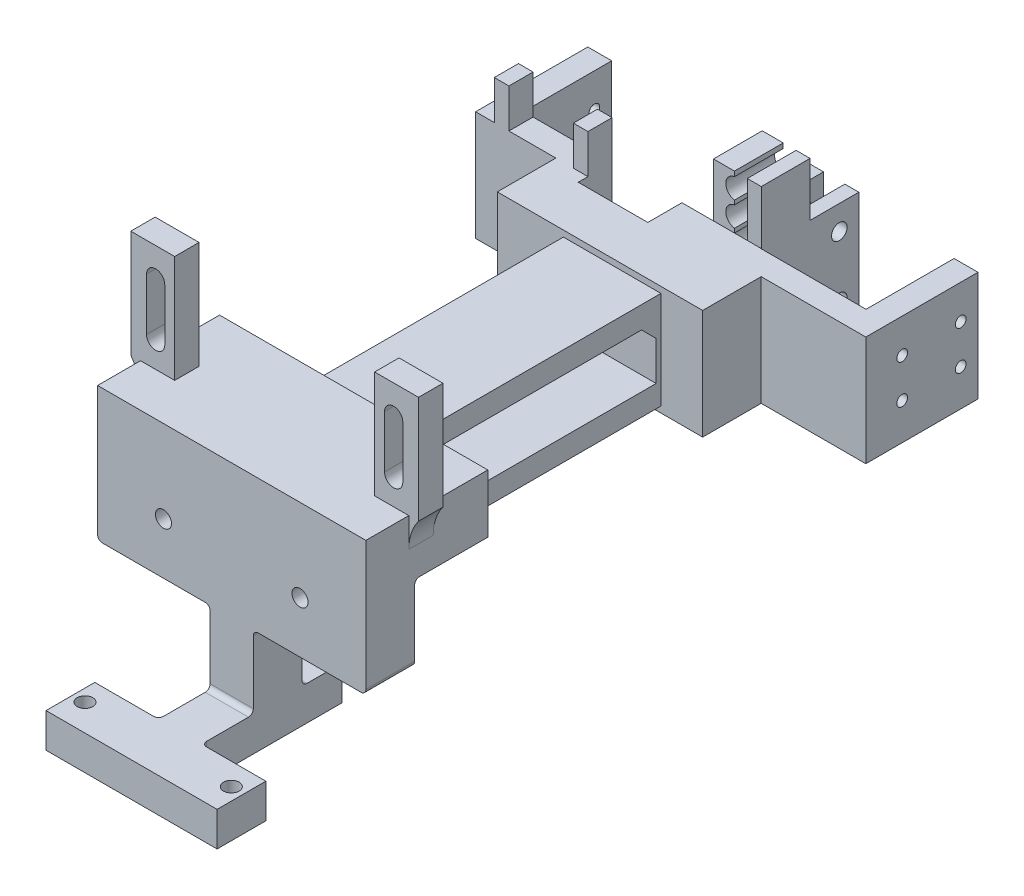
SolidWorks part; units mm, degrees
ref_plane "Front Plane" through (0, 0, 0) normal (0, 0, 1) x (1, 0, 0)
ref_plane "Top Plane" through (0, 0, 0) normal (0, 1, 0) x (1, 0, 0)
ref_plane "Right Plane" through (0, 0, 0) normal (1, 0, 0) x (0, 0, -1)
sketch "草图1" plane through (0, 0, 0) normal (0, 0, 1) x (1, 0, 0)
  line L0 (0, 0) -> (8.5606, 9.7835) construction
  line L1 (-17.5, 20) -> (17.5, 20)
  line L2 (-17.5, 20) -> (-17.5, -20)
  line L3 (-17.5, -20) -> (17.5, -20)
  line L4 (17.5, 20) -> (17.5, -20)
  line L5 (-17.5, 20) -> (0, 0) construction
  line L6 (-17.5, -20) -> (-8.5606, -9.7835) construction
  line L7 (8.5606, -9.7835) -> (17.5, -20) construction
  arc A0 (-12.9135, -1.4975) -> (-8.5606, -9.7835) centre (0, 0) ccw construction
  arc A5 (-1.4975, 12.9135) -> (-12.9135, 1.4975) centre (0, 0) ccw construction
  arc A6 (1.4975, -12.9135) -> (12.9135, -1.4975) centre (0, 0) ccw construction
  arc A8 (12.9135, 1.4975) -> (1.4975, 12.9135) centre (0, 0) ccw construction
  point P0 (0, 0)
  point P19 (0, 0)
  dimension "D1" = 26
  dimension "D2" = 35
  dimension "D3" = 40
extrude "凸台-拉伸1" add sketch "草图1" along normal blind 5
sketch "草图2" plane through (0, 0, 5) normal (0, 0, 1) x (1, 0, 0)
  line L1 (-10, 10) -> (10, 10)
  line L2 (-10, 10) -> (-10, -10)
  line L3 (-10, -10) -> (10, -10)
  line L4 (10, 10) -> (10, -10)
  line L5 (-10, 10) -> (10, -10) construction
  line L6 (-10, -10) -> (10, 10) construction
  point P0 (0, 0)
  dimension "D1" = 20
  dimension "D2" = 20
extrude "凸台-拉伸2" add sketch "草图2" along normal blind 65
sketch "草图3" plane through (-10, 0, 0) normal (-1, 0, 0) x (0, 0, 1)
  line L1 (9.5, -5.5) -> (65.5, -5.5)
  line L2 (65.5, -5.5) -> (65.5, 5.5)
  line L3 (65.5, 5.5) -> (9.5, 5.5)
  line L4 (5, 10) -> (5, -10)
  line L5 (5, -10) -> (70, -10)
  line L6 (70, -10) -> (70, 10)
  line L7 (70, 10) -> (5, 10)
  line L8 (5, 10) -> (5, -10)
  line L9 (5, -10) -> (70, -10)
  line L10 (70, -10) -> (70, 10)
  line L11 (70, 10) -> (5, 10)
  line L12 (9.5, 5.5) -> (5, 5.5)
  line L13 (5, 5.5) -> (5, -5.5)
  line L14 (5, -5.5) -> (9.5, -5.5)
  line L16 (9.5, 5.5) -> (9.5, -5.5) construction
  dimension "D1" = 0
  dimension "D2" = 4.5
extrude "切除-拉伸1" cut sketch "草图3" against normal through all contours L3 L16 L1 L2 | L16 L12 L8 L14
sketch "草图5" plane through (0, 0, 70) normal (0, 0, 1) x (1, 0, 0)
  line L1 (-27.5, 10) -> (27.5, 10)
  line L2 (-27.5, 10) -> (-27.5, -10)
  line L3 (-27.5, -10) -> (27.5, -10)
  line L4 (27.5, 10) -> (27.5, -10)
  line L5 (-27.5, 10) -> (27.5, -10) construction
  line L6 (-27.5, -10) -> (27.5, 10) construction
  point P0 (0, 0)
  dimension "D1" = 20
  dimension "D2" = 55
extrude "凸台-拉伸3" add sketch "草图5" along normal blind 25
sketch "草图6" plane through (0, 0, 95) normal (0, 0, 1) x (1, 0, 0)
  circle A0 centre (-10.5, 24.851) radius 28
  dimension "D1" = 56
sketch "草图7" plane through (0, 0, 95) normal (0, 0, 1) x (1, 0, 0)
  line L0 (-27.5, 0) -> (27.5, 0) construction
  circle A0 centre (-14, 0) radius 1.6
  circle A1 centre (14, 0) radius 1.6
  dimension "D1" = 3.2
  dimension "D2" = 3.2
  dimension "D3" = 14
sketch "草图8" plane through (0, 0, 95) normal (0, 0, 1) x (1, 0, 0)
  line L0 (0, 0) -> (0, 38.7241) construction
  line L1 (17.5, 20) -> (-17.5, 20) construction
  circle A0 centre (0, 20) radius 1.9754 construction
  circle A1 centre (0, 20) radius 14.0625
  dimension "D1" = 28.125
sketch "草图9" plane through (0, 0, 95) normal (0, 0, 1) x (1, 0, 0)
  line L1 (0, -51.5757) -> (0, 13.3029) construction
  line L2 (14, -3.0427) -> (-14, -3.0427) construction
  line L3 (27.5, 10) -> (-27.5, 10) construction
  line L4 (-8.5, -51.5757) -> (8.5, -51.5757) construction
  circle A1 centre (-14, -3.0427) radius 1.65
  circle A2 centre (14, -3.0427) radius 1.65
  dimension "D1" = 14
  dimension "D3" = 3.3
  dimension "D2" = 13.0427
  dimension "D4" = 14
extrude "切除-拉伸3" cut sketch "草图9" against normal blind 27
sketch "草图10" plane through (0, 10, 0) normal (0, 1, 0) x (1, 0, 0)
  line L1 (-27.5, -70) -> (27.5, -70)
  line L2 (-27.5, -70) -> (-27.5, -95)
  line L3 (-27.5, -95) -> (27.5, -95)
  line L4 (27.5, -70) -> (27.5, -95)
extrude "凸台-拉伸4" add sketch "草图10" along normal blind 4.9
sketch "草图11" plane through (0, 14.9, 0) normal (0, 1, 0) x (1, 0, 0)
  line L0 (-27.5, -70) -> (-27.5, -95) construction
  line L1 (-27.5, -81.2) -> (-20.5, -81.2)
  line L2 (-27.5, -81.2) -> (-27.5, -86.2)
  line L3 (-27.5, -86.2) -> (-20.5, -86.2)
  line L4 (-20.5, -81.2) -> (-20.5, -86.2)
  line L5 (-20.5, -94.35) -> (-20.5, -85.7) construction
  line L6 (-25.1, -86.2) -> (-20.5, -86.2) construction
  line L7 (27.5, -95) -> (27.5, -70) construction
  line L8 (27.5, -86.2) -> (20.5, -86.2)
  line L9 (27.5, -86.2) -> (27.5, -81.2)
  line L10 (27.5, -81.2) -> (20.5, -81.2)
  line L11 (20.5, -86.2) -> (20.5, -81.2)
  line L12 (20.5, -65.7) -> (20.5, -85.7) construction
  dimension "D1" = 5
  dimension "D2" = 5
extrude "凸台-拉伸5" add sketch "草图11" along normal blind 21
sketch "草图12" plane through (0, 0, 86.2) normal (0, 0, 1) x (1, 0, 0)
  circle A0 centre (-24.4, 29.9) radius 1.5
  circle A1 centre (-24.4, 19.9) radius 1.5
  circle A2 centre (24.4, 19.9) radius 1.5
  circle A3 centre (24.4, 29.9) radius 1.5
  dimension "D1" = 3
extrude "切除-拉伸4" [suppressed] cut sketch "草图12" against normal blind 21
chamfer "倒角2" distance 10 angle 45 1 edges at (0, -5.5, 65.5)
chamfer "倒角3" distance 3 angle 45 1 edges at (0, 10, 70)
chamfer "倒角4" distance 2 angle 45 1 edges at (0, -10, 5)
sketch "草图13" plane through (0, 0, 5) normal (0, 0, 1) x (1, 0, 0)
  circle A0 centre (0, -13) radius 2.5
  dimension "D1" = 5
sketch "草图14" plane through (27.5, 0, 0) normal (1, 0, 0) x (0, 0, -1)
  circle A0 centre (-79.3333, -5.771) radius 1.5
  circle A1 centre (-65.7124, -5.771) radius 1.5
extrude "切除-拉伸6" [suppressed] cut sketch "草图14" against normal through all
sketch "草图15" plane through (0, 0, 70) normal (0, 0, -1) x (-1, 0, 0)
  line L0 (0, 0) -> (0, -6.8076) construction
  line L1 (10, 13) -> (10, -10) construction
  line L2 (10, 1.9573) -> (29.1308, 1.9573)
  line L3 (10, 1.9573) -> (10, -8.0427)
  line L5 (29.1308, 1.9573) -> (29.1308, -8.0427)
  line L6 (14, -3.0427) -> (8.2324, -3.0427) construction
  line L7 (-14, -3.0427) -> (-8.2324, -3.0427) construction
  line L8 (-29.1308, 1.9573) -> (-29.1308, -8.0427)
  line L10 (-10, 1.9573) -> (-10, -8.0427)
  line L11 (-10, 1.9573) -> (-29.1308, 1.9573)
  line L14 (-29.1308, -8.0427) -> (-29.1308, -10)
  line L15 (-29.1308, -10) -> (-10, -10)
  line L16 (-10, -8.0427) -> (-10, -10)
  line L18 (10, -8.0427) -> (10, -10)
  line L19 (10, -10) -> (29.1308, -10)
  line L20 (29.1308, -8.0427) -> (29.1308, -10)
  point P13 (10, -3.0427)
  dimension "D1" = 10
extrude "切除-拉伸7" cut sketch "草图15" against normal blind 15
sketch "草图16" plane through (-10, 0, 0) normal (-1, 0, 0) x (0, 0, 1)
  line L0 (5, -5.5) -> (55.5, -5.5) construction
  line L1 (5, 5.5) -> (17.9846, 5.5)
  line L2 (5, 5.5) -> (5, -5.5)
  line L3 (5, -5.5) -> (17.9846, -5.5)
  line L4 (17.9846, 5.5) -> (17.9846, -5.5)
extrude "凸台-拉伸6" add sketch "草图16" against normal up to surface (20 mm away) up to face at (10, 0.7242, 45.4231)
chamfer "倒角5" distance 3 angle 45 1 edges at (0, 5.5, 17.9846)
sketch "草图19" plane through (0, 0, 86.2) normal (0, 0, 1) x (1, 0, 0)
  circle A0 centre (-24.4, 29.9) radius 1.6
  circle A1 centre (-24.4, 19.9) radius 1.6
  circle A2 centre (24.4, 19.9) radius 1.6
  circle A3 centre (24.4, 29.9) radius 1.6
  dimension "D1" = 3.2
extrude "切除-拉伸10" cut sketch "草图19" against normal blind 10
fillet "圆角1" radius 5 4 edges at (17.5, 20, 2.5) (17.5, -20, 2.5) (-17.5, -20, 2.5) (-17.5, 20, 2.5)
ref_plane "基准面1" through (0, 0, 0) normal (0, 1, 0) x (1, 0, 0)
sketch "草图20" plane through (-17.5, 0, 0) normal (-1, 0, 0) x (0, 0, 1)
  line L0 (0, 15) -> (0, -15) construction
  line L1 (0, 11.25) -> (5, 11.25)
  line L2 (0, 11.25) -> (0, -11.25)
  line L3 (0, -11.25) -> (5, -11.25)
  line L4 (5, 11.25) -> (5, -11.25)
  line L5 (0, 11.25) -> (-6.5, 11.25) construction
  line L6 (5, 15) -> (5, -15) construction
extrude "凸台-拉伸7" add sketch "草图20" along normal up to surface (17.5 mm away)
sketch "草图21" plane through (-35, 0, 0) normal (-1, 0, 0) x (0, 0, 1)
  line L4 (0, -11.25) -> (5, -11.25)
  line L5 (5, -11.25) -> (5, 11.25)
  line L6 (5, 11.25) -> (0, 11.25)
  line L7 (0, 11.25) -> (0, -11.25)
  line L8 (0, -11.25) -> (5, -11.25)
  line L9 (5, -11.25) -> (5, 11.25)
  line L10 (5, 11.25) -> (0, 11.25)
  line L11 (0, 11.25) -> (0, -11.25)
  dimension "D1" = 0
extrude "凸台-拉伸8" add sketch "草图21" along normal blind 5
sketch "草图22" plane through (0, 0, 0) normal (0, 0, -1) x (-1, 0, 0)
  line L0 (40, 11.25) -> (17.5, 11.25) construction
  line L1 (40, -11.25) -> (35, -11.25)
  line L2 (40, -11.25) -> (40, 11.25)
  line L3 (40, 11.25) -> (35, 11.25)
  line L4 (35, -11.25) -> (35, 11.25)
  line L5 (35, -11.25) -> (35, 11.25) construction
extrude "凸台-拉伸9" add sketch "草图22" along normal blind 10
sketch "草图23" plane through (0, 0, 0) normal (0, 0, -1) x (-1, 0, 0)
  line L0 (35, -11.25) -> (17.5, -11.25) construction
  line L1 (18, -11.25) -> (13, -11.25)
  line L2 (18, -11.25) -> (18, 11.25)
  line L3 (18, 11.25) -> (13, 11.25)
  line L4 (13, -11.25) -> (13, 11.25)
  line L5 (18, -11.25) -> (18, 11.25) construction
  dimension "D1" = 5
extrude "凸台-拉伸10" add sketch "草图23" along normal blind 10
sketch "草图24" plane through (-18, 0, 0) normal (-1, 0, 0) x (0, 0, 1)
  line L1 (-10, 11.25) -> (-6.7, 11.25)
  line L2 (-10, 11.25) -> (-10, -11.25)
  line L3 (-10, -11.25) -> (-6.7, -11.25)
  line L4 (-6.7, 11.25) -> (-6.7, -11.25)
  dimension "D1" = 3.3
extrude "凸台-拉伸11" add sketch "草图24" along normal blind 4
sketch "草图25" plane through (-35, 0, 0) normal (1, 0, 0) x (0, 0, -1)
  line L0 (10, -11.25) -> (0, -11.25) construction
  line L1 (10, 11.25) -> (6.7, 11.25)
  line L2 (10, 11.25) -> (10, -11.25)
  line L3 (10, -11.25) -> (6.7, -11.25)
  line L4 (6.7, 11.25) -> (6.7, -11.25)
  dimension "D1" = 3.3
sketch "草图26" plane through (17.5, 0, 0) normal (1, 0, 0) x (0, 0, -1)
  line L1 (-5, 11.25) -> (0, 11.25)
  line L2 (-5, 11.25) -> (-5, -11.25)
  line L3 (-5, -11.25) -> (0, -11.25)
  line L4 (0, 11.25) -> (0, -11.25)
extrude "凸台-拉伸13" add sketch "草图26" along normal up to surface (17.5 mm away)
sketch "草图27" plane through (35, 0, 0) normal (1, 0, 0) x (0, 0, -1)
  line L4 (-5, -11.25) -> (0, -11.25)
  line L5 (0, -11.25) -> (0, 11.25)
  line L6 (0, 11.25) -> (-5, 11.25)
  line L7 (-5, 11.25) -> (-5, -11.25)
  line L8 (-5, -11.25) -> (0, -11.25)
  line L9 (0, -11.25) -> (0, 11.25)
  line L10 (0, 11.25) -> (-5, 11.25)
  line L11 (-5, 11.25) -> (-5, -11.25)
  dimension "D1" = 0
extrude "凸台-拉伸14" add sketch "草图27" along normal blind 5
sketch "草图28" plane through (0, 0, 0) normal (0, 0, -1) x (-1, 0, 0)
  line L0 (-40, -11.25) -> (-17.5, -11.25) construction
  line L1 (-40, 11.25) -> (-35, 11.25)
  line L2 (-40, 11.25) -> (-40, -11.25)
  line L3 (-40, -11.25) -> (-35, -11.25)
  line L4 (-35, 11.25) -> (-35, -11.25)
  line L5 (-35, -11.25) -> (-35, 11.25) construction
extrude "凸台-拉伸15" add sketch "草图28" along normal up to surface (10 mm away) up to face at (-17.5, 0, -10)
sketch "草图29" plane through (0, 0, 0) normal (0, 0, -1) x (-1, 0, 0)
  line L0 (-35, 11.25) -> (-17.5, 11.25) construction
  line L1 (-18, 11.25) -> (-13, 11.25)
  line L2 (-18, 11.25) -> (-18, -11.25)
  line L3 (-18, -11.25) -> (-13, -11.25)
  line L4 (-13, 11.25) -> (-13, -11.25)
  line L5 (-18, -11.25) -> (-18, 11.25) construction
  line L6 (-35, -11.25) -> (-17.5, -11.25) construction
  dimension "D1" = 5
extrude "凸台-拉伸16" add sketch "草图29" along normal up to surface (10 mm away) up to face at (37.5, 0, -10)
sketch "草图30" plane through (35, 0, 0) normal (-1, 0, 0) x (0, 0, 1)
  line L0 (-10, -11.25) -> (0, -11.25) construction
  line L1 (-10, 11.25) -> (-6.6, 11.25)
  line L2 (-10, 11.25) -> (-10, -11.25)
  line L3 (-10, -11.25) -> (-6.6, -11.25)
  line L4 (-6.6, 11.25) -> (-6.6, -11.25)
  dimension "D1" = 3.4
sketch "草图31" plane through (18, 0, 0) normal (1, 0, 0) x (0, 0, -1)
  line L0 (10, 11.25) -> (0, 11.25) construction
  line L1 (10, -11.25) -> (6.6, -11.25)
  line L2 (10, -11.25) -> (10, 11.25)
  line L3 (10, 11.25) -> (6.6, 11.25)
  line L4 (6.6, -11.25) -> (6.6, 11.25)
  dimension "D1" = 3.4
extrude "凸台-拉伸18" add sketch "草图31" along normal blind 4
sketch "草图32" plane through (0, 0, 5) normal (0, 0, 1) x (1, 0, 0)
  circle A0 centre (-32.5, 3.75) radius 1
  circle A1 centre (-32.5, -4.25) radius 1
  circle A2 centre (-20.5, 3.75) radius 1
  circle A3 centre (-20.5, -4.25) radius 1
  circle A4 centre (20.5, 3.75) radius 1
  circle A5 centre (20.5, -4.25) radius 1
  circle A6 centre (32.5, -4.25) radius 1
  circle A7 centre (32.5, 3.75) radius 1
  dimension "D1" = 2
  dimension "D2" = 2
  dimension "D3" = 2
sketch "草图33" plane through (0, -10, 0) normal (0, -1, 0) x (1, 0, 0)
  line L0 (-27.5, 70) -> (-27.5, 85) construction
  line L1 (-27.5, 62.1642) -> (27.5, 62.1642)
  line L2 (-27.5, 62.1642) -> (-27.5, 106.0669)
  line L3 (-27.5, 106.0669) -> (27.5, 106.0669)
  line L4 (27.5, 62.1642) -> (27.5, 106.0669)
extrude "凸台-拉伸19" [suppressed] add sketch "草图33" along normal up to surface (25.5757 mm away)
sketch "草图34" [suppressed] plane through (0, -10, 0) normal (0, 1, 0) x (1, 0, 0)
  line L0 (0, -106.0669) -> (0, -40) construction
  line L1 (27.5, -106.0669) -> (-27.5, -106.0669) construction
  line L2 (27.5, -40) -> (-27.5, -40) construction
  line L4 (-27.5, -40) -> (-6, -40)
  line L5 (-27.5, -40) -> (-27.5, -77.2915)
  line L6 (-27.5, -77.2915) -> (-6, -77.2915)
  line L7 (-6, -40) -> (-6, -77.2915)
  line L8 (27.5, -40) -> (6, -40)
  line L9 (27.5, -40) -> (27.5, -77.2915)
  line L10 (27.5, -77.2915) -> (6, -77.2915)
  line L11 (6, -40) -> (6, -77.2915)
  line L12 (27.5, -106.0669) -> (-27.5, -106.0669)
  line L13 (27.5, -106.0669) -> (27.5, -65)
  line L14 (27.5, -65) -> (-27.5, -65)
  line L15 (-27.5, -106.0669) -> (-27.5, -65)
  dimension "D1" = 6
  dimension "D2" = 6
extrude "切除-拉伸12" [suppressed] cut sketch "草图34" against normal blind 18
sketch "草图35" [suppressed] plane through (0, -35.5757, 0) normal (0, -1, 0) x (1, 0, 0)
  line L0 (-17.5, 85.6) -> (-17.5, 41.6) construction
  line L1 (-27.5, 62.1642) -> (-4.8154, 62.1642)
  line L2 (-27.5, 62.1642) -> (-27.5, 81.8991)
  line L3 (-17.5, 81.8991) -> (-4.8154, 81.8991)
  line L4 (-4.8154, 62.1642) -> (-4.8154, 81.8991)
  line L5 (27.5, 62.1642) -> (3.7618, 62.1642)
  line L6 (27.5, 62.1642) -> (27.5, 81.8624)
  line L7 (17.5, 81.8991) -> (3.7618, 81.8991)
  line L8 (3.7618, 62.1642) -> (3.7618, 81.8991)
  line L9 (-27.5, 106.0669) -> (-17.5, 106.0669)
  line L10 (-27.5, 106.0669) -> (-27.5, 81.8991)
  line L12 (-17.5, 106.0669) -> (-17.5, 81.8991)
  line L14 (27.5, 106.0669) -> (17.5, 106.0669)
  line L17 (17.5, 106.0669) -> (17.5, 81.8991)
  line L19 (27.5, 81.8624) -> (27.5, 106.0669)
extrude "切除-拉伸13" [suppressed] cut sketch "草图35" against normal blind 11
sketch "草图36" [suppressed] plane through (0, -35.5757, 0) normal (0, -1, 0) x (1, 0, 0)
  line L0 (17.5, 106.0669) -> (17.5, 81.8991) construction
  line L1 (-17.5, 81.8991) -> (17.5, 81.8991)
  line L2 (-17.5, 81.8991) -> (-17.5, 95.6286)
  line L3 (-17.5, 95.6286) -> (17.5, 95.6286)
  line L4 (17.5, 81.8991) -> (17.5, 95.6286)
extrude "切除-拉伸14" [suppressed] cut sketch "草图36" against normal blind 5
sketch "草图37" [suppressed] plane through (0, -35.5757, 0) normal (0, -1, 0) x (1, 0, 0)
  line L0 (3.7618, 81.8991) -> (3.7618, 62.1642) construction
  line L1 (-4.8154, 62.1642) -> (3.7618, 62.1642)
  line L2 (-4.8154, 62.1642) -> (-4.8154, 72.6172)
  line L3 (-4.8154, 72.6172) -> (3.7618, 72.6172)
  line L4 (3.7618, 62.1642) -> (3.7618, 72.6172)
extrude "切除-拉伸15" [suppressed] cut sketch "草图37" against normal up to surface (5 mm away)
fillet "圆角2" [suppressed] radius 1
sketch "草图38" [suppressed] plane through (0, -28, 0) normal (0, 1, 0) x (1, 0, 0)
  circle A0 centre (-15, -80.1116) radius 1.5
  circle A1 centre (15, -80.1116) radius 1.5
extrude "切除-拉伸16" [suppressed] cut sketch "草图38" against normal up to surface (7.5757 mm away)
sketch "草图39" plane through (-17.5, 0, 0) normal (-1, 0, 0) x (0, 0, 1)
  line L1 (0, 11.25) -> (7.1368, 11.25)
  line L2 (0, 11.25) -> (0, 24.7683)
  line L3 (0, 24.7683) -> (7.1368, 24.7683)
  line L4 (7.1368, 11.25) -> (7.1368, 24.7683)
  line L5 (0, -11.25) -> (8.1393, -11.25)
  line L6 (0, -11.25) -> (0, -21.7723)
  line L7 (0, -21.7723) -> (8.1393, -21.7723)
  line L8 (8.1393, -11.25) -> (8.1393, -21.7723)
extrude "切除-拉伸17" cut sketch "草图39" against normal up to surface (35 mm away) up to face at (17.5, 13.125, 2.5)
sketch "草图40" plane through (0, -10, 0) normal (0, -1, 0) x (1, 0, 0)
  line L1 (27.5, 85) -> (-27.5, 85)
  line L2 (27.5, 85) -> (27.5, 95)
  line L3 (27.5, 95) -> (-27.5, 95)
  line L4 (-27.5, 85) -> (-27.5, 95)
extrude "凸台-拉伸20" add sketch "草图40" along normal up to surface (25.5757 mm away)
sketch "草图41" plane through (0, 0, 95) normal (0, 0, 1) x (1, 0, 0)
  line L0 (27.5, -35.5757) -> (-27.5, -35.5757) construction
  line L1 (-4.4244, -35.5757) -> (4.4244, -35.5757)
  line L2 (-4.4244, -35.5757) -> (-4.4244, -28.5296)
  line L3 (-4.4244, -28.5296) -> (4.4244, -28.5296)
  line L4 (4.4244, -35.5757) -> (4.4244, -28.5296)
  line L5 (4.4244, -35.5757) -> (-4.4244, -28.5296) construction
  line L6 (0, -37.5757) -> (0, -41.8305) construction
  line L7 (-8.5, -37.5757) -> (8.5, -37.5757) construction
  point P11 (0, -32.0526)
extrude "凸台-拉伸21" add sketch "草图41" along normal up to surface (20.578 mm away)
sketch "草图42" plane through (-4.4244, 0, 0) normal (-1, 0, 0) x (0, 0, 1)
  line L0 (115.578, -28.5296) -> (95, -28.5296) construction
  line L1 (115.578, -35.5757) -> (76.7852, -35.5757)
  line L2 (115.578, -35.5757) -> (115.578, -28.5296)
  line L3 (115.578, -28.5296) -> (76.7852, -28.5296)
  line L4 (76.7852, -35.5757) -> (76.7852, -28.5296)
extrude "凸台-拉伸22" add sketch "草图42" along normal up to surface (13.0756 mm away) and the other way blind 22
sketch "草图43" plane through (0, -35.5757, 0) normal (0, -1, 0) x (1, 0, 0)
  line L1 (27.5, 76.7852) -> (4.4244, 76.7852)
  line L2 (27.5, 76.7852) -> (27.5, 105.578)
  line L3 (27.5, 105.578) -> (4.4244, 105.578)
  line L4 (4.4244, 76.7852) -> (4.4244, 105.578)
  line L6 (-27.5, 76.7852) -> (-4.4244, 76.7852)
  line L7 (-27.5, 76.7852) -> (-27.5, 105.578)
  line L8 (-27.5, 105.578) -> (-4.4244, 105.578)
  line L9 (-4.4244, 76.7852) -> (-4.4244, 105.578)
  line L11 (17.5756, 76.7852) -> (-17.5, 76.7852) construction
  line L13 (17.5756, 115.578) -> (-17.5, 115.578) construction
  dimension "D1" = 10
extrude "切除-拉伸18" cut sketch "草图43" against normal blind 22
fillet "圆角3" radius 1 11 edges at (-27.5, -13.5757, 90) (27.5, -13.5757, 90) (4.4244, -13.5757, 90) (18.75, 1.9573, 85) (-4.4244, -13.5757, 90) (0, -10, 85) (-18.75, 1.9573, 85) (0, -28.5296, 95) (0, -28.5296, 85) (-4.4244, -32.0526, 105.578) (4.4244, -32.0526, 105.578)
sketch "草图46" plane through (0, 0, 0) normal (0, 0, -1) x (-1, 0, 0)
  line L0 (-13, -11.25) -> (13, -11.25) construction
  line L1 (-13, 11.25) -> (-3.7618, 11.25)
  line L2 (-13, 11.25) -> (-13, -11.25)
  line L3 (-13, -11.25) -> (-3.7618, -11.25)
  line L4 (-3.7618, 11.25) -> (-3.7618, -11.25)
extrude "凸台-拉伸26" add sketch "草图46" along normal blind 10
sketch "草图47" plane through (0, 0, -10) normal (0, 0, -1) x (-1, 0, 0)
  line L0 (0, 120.494) -> (0, -21.6004) construction
  line L1 (-3.7618, 11.25) -> (-22, 11.25) construction
  line L2 (-8.0664, 11.25) -> (-10.7005, 11.25)
  line L3 (-10.7005, 11.25) -> (-10.7005, -11.25)
  line L4 (-22, -11.25) -> (-3.7618, -11.25) construction
  line L5 (-10.7005, -11.25) -> (-6.3328, -11.25)
  line L6 (-6.3328, -11.25) -> (-6.3328, -9.5796) construction
  line L7 (-8.0664, -7.9) -> (-8.0664, -8.75)
  line L8 (-8.0664, -2.9) -> (-8.0664, -3.75)
  line L9 (-8.0664, 7.1) -> (-8.0664, 6.25)
  line L10 (-8.0664, 2.1) -> (-8.0664, 1.25)
  circle A0 centre (0, 109.494) radius 11 construction
  arc A1 (-8.0664, 11.25) -> (-8.0664, 7.1) centre (-8.3894, 9.175) cw
  arc A2 (-8.0664, 6.25) -> (-8.0664, 2.1) centre (-8.3894, 4.175) cw
  arc A3 (-8.0664, 1.25) -> (-8.0664, -2.9) centre (-8.3894, -0.825) cw
  arc A4 (-8.0664, -3.75) -> (-8.0664, -7.9) centre (-8.3894, -5.825) cw
  arc A5 (-8.0664, -8.75) -> (-6.3328, -11.25) centre (-8.3894, -10.825) cw
  dimension "D1" = 2.1
  dimension "D2" = 5
extrude "切除-拉伸19" cut sketch "草图47" against normal blind 10
sketch "草图48" plane through (0, -28.5296, 0) normal (0, 1, 0) x (1, 0, 0)
  circle A0 centre (15, -110.0896) radius 1.6
  circle A1 centre (-15, -110.0896) radius 1.6
  dimension "D1" = 3.2
extrude "切除-拉伸20" cut sketch "草图48" against normal blind 10
sketch "草图49" plane through (0, 0, 86.2) normal (0, 0, 1) x (1, 0, 0)
  line L0 (0, 0) -> (0, 23.1634) construction
  line L1 (-24.4, 29.9) -> (-24.4, 19.1657) construction
  line L2 (-22.5287, 29.9) -> (-22.5287, 19.1657)
  line L3 (-26.2713, 29.9) -> (-26.2713, 19.1657)
  line L4 (24.4, 29.9) -> (24.4, 19.1657) construction
  line L5 (22.5287, 29.9) -> (22.5287, 19.1657)
  line L6 (26.2713, 29.9) -> (26.2713, 19.1657)
  arc A0 (-22.5287, 29.9) -> (-26.2713, 29.9) centre (-24.4, 29.9) ccw
  arc A1 (-26.2713, 19.1657) -> (-22.5287, 19.1657) centre (-24.4, 19.1657) ccw
  arc A2 (22.5287, 29.9) -> (26.2713, 29.9) centre (24.4, 29.9) cw
  arc A3 (26.2713, 19.1657) -> (22.5287, 19.1657) centre (24.4, 19.1657) cw
  point P6 (-24.4, 24.5328)
  point P13 (24.4, 24.5328)
extrude "切除-拉伸21" cut sketch "草图49" against normal blind 10
sketch "草图50" plane through (0, 0, -10) normal (0, 0, -1) x (-1, 0, 0)
  line L0 (-22, -11.25) -> (-10.7005, -11.25) construction
  line L1 (-3.7618, 11.25) -> (-6.3328, 11.25)
  line L2 (-3.7618, 11.25) -> (-3.7618, -11.25)
  line L3 (-3.7618, -11.25) -> (-6.3328, -11.25)
  line L4 (-6.3328, 11.25) -> (-6.3328, -11.25)
  line L5 (-10.7005, 11.25) -> (-13.5656, 11.25)
  line L6 (-10.7005, 11.25) -> (-10.7005, -11.25)
  line L7 (-10.7005, -11.25) -> (-13.5656, -11.25)
  line L8 (-13.5656, 11.25) -> (-13.5656, -11.25)
extrude "凸台-拉伸27" add sketch "草图50" along normal blind 10
sketch "草图53" plane through (0, 11.25, 0) normal (0, 1, 0) x (1, 0, 0)
  line L1 (8.0664, 10) -> (3.7618, 10)
  line L2 (8.0664, 10) -> (8.0664, 0)
  line L3 (8.0664, 0) -> (3.7618, 0)
  line L4 (3.7618, 10) -> (3.7618, 0)
  line L5 (13.5656, 10) -> (10.7005, 10)
  line L6 (13.5656, 10) -> (13.5656, 0)
  line L7 (13.5656, 0) -> (10.7005, 0)
  line L8 (10.7005, 10) -> (10.7005, 0)
extrude "凸台-拉伸28" add sketch "草图53" along normal blind 11
sketch "草图51" plane through (13.5656, 0, 0) normal (1, 0, 0) x (0, 0, -1)
  line L0 (15, 11.25) -> (15, -11.25) construction
  line L1 (20, 11.25) -> (10, 11.25) construction
  line L2 (20, -11.25) -> (10, -11.25) construction
  line L3 (20, 11.25) -> (20, -11.25) construction
  circle A0 centre (16, 6.25) radius 1.6
  circle A1 centre (16, -6.25) radius 1.6
  dimension "D1" = 3.2
  dimension "D2" = 5
  dimension "D3" = 5
  dimension "D4" = 4
extrude "切除-拉伸22" cut sketch "草图51" against normal blind 12
sketch "草图52" plane through (0, 11.25, 0) normal (0, 1, 0) x (1, 0, 0)
  line L0 (-26.5, 0) -> (-26.5, 6.7) construction
  line L1 (-35, 0) -> (-18, 0) construction
  line L2 (0, 0) -> (0, 4.3666) construction
  line L3 (-35.1, 6.75) -> (-17.9, 6.75)
  line L4 (-35.1, 6.75) -> (-35.1, -0.05)
  line L5 (-35.1, -0.05) -> (-17.9, -0.05)
  line L6 (-17.9, 6.75) -> (-17.9, -0.05)
  line L7 (-35.1, 6.75) -> (-17.9, -0.05) construction
  line L8 (-35.1, -0.05) -> (-17.9, 6.75) construction
  line L9 (35.1, -0.05) -> (17.9, -0.05)
  line L10 (17.9, 6.75) -> (17.9, -0.05)
  line L11 (35.1, 6.75) -> (17.9, 6.75)
  line L12 (35.1, 6.75) -> (35.1, -0.05)
  point P4 (-26.5, 3.35)
  dimension "D1" = 17.2
  dimension "D2" = 6.8
extrude "切除-拉伸23" cut sketch "草图52" against normal blind 39
ref_plane "基准面2" through (5.0473, 0, 0) normal (-1, 0, 0) x (0, 0, 1)
sketch "草图54" plane through (0, 0, -10) normal (0, 0, -1) x (-1, 0, 0)
  line L0 (-8.0664, 21.25) -> (-10.7005, 21.25)
  line L1 (-10.7005, 21.25) -> (-10.7005, -1.25)
  line L2 (-10.7005, -1.25) -> (-6.3328, -1.25)
  line L3 (-8.0664, 1.25) -> (-8.0664, 2.1)
  line L4 (-8.0664, 6.25) -> (-8.0664, 7.1)
  line L5 (-8.0664, 11.25) -> (-8.0664, 12.1)
  line L6 (-8.0664, 16.25) -> (-8.0664, 17.1)
  line L7 (-8.0664, 11.25) -> (-10.7005, 11.25)
  line L8 (-10.7005, 11.25) -> (-10.7005, -11.25)
  line L10 (-8.0664, -8.75) -> (-8.0664, -7.9)
  line L11 (-8.0664, -3.75) -> (-8.0664, -2.9)
  line L12 (-8.0664, 1.25) -> (-8.0664, 2.1)
  line L13 (-8.0664, 6.25) -> (-8.0664, 7.1)
  line L15 (-10.7005, 11.25) -> (-10.7005, -11.25)
  line L17 (-8.0664, -8.75) -> (-8.0664, -7.9)
  line L18 (-8.0664, -3.75) -> (-8.0664, -2.9)
  line L19 (-8.0664, 1.25) -> (-8.0664, 2.1)
  line L20 (-8.0664, 6.25) -> (-8.0664, 7.1)
  line L48 (-8.0664, 11.25) -> (-10.7005, 11.25)
  line L50 (-10.7005, -11.25) -> (-6.3328, -11.25)
  line L51 (-10.7005, -11.25) -> (-6.3328, -11.25)
  arc A0 (-8.0664, 17.1) -> (-8.0664, 21.25) centre (-8.3894, 19.175) ccw
  arc A1 (-6.3328, -1.25) -> (-8.0664, 1.25) centre (-8.3894, -0.825) ccw
  arc A2 (-8.0664, 2.1) -> (-8.0664, 6.25) centre (-8.3894, 4.175) ccw
  arc A3 (-8.0664, 7.1) -> (-8.0664, 11.25) centre (-8.3894, 9.175) ccw
  arc A4 (-8.0664, 12.1) -> (-8.0664, 16.25) centre (-8.3894, 14.175) ccw
  arc A5 (-8.0664, 7.1) -> (-8.0664, 11.25) centre (-8.3894, 9.175) ccw
  arc A6 (-6.3328, -11.25) -> (-8.0664, -8.75) centre (-8.3894, -10.825) ccw
  arc A7 (-8.0664, -7.9) -> (-8.0664, -3.75) centre (-8.3894, -5.825) ccw
  arc A8 (-8.0664, -2.9) -> (-8.0664, 1.25) centre (-8.3894, -0.825) ccw
  arc A9 (-8.0664, 2.1) -> (-8.0664, 6.25) centre (-8.3894, 4.175) ccw
  arc A10 (-8.0664, 7.1) -> (-8.0664, 11.25) centre (-8.3894, 9.175) ccw
  arc A11 (-6.3328, -11.25) -> (-8.0664, -8.75) centre (-8.3894, -10.825) ccw
  arc A12 (-8.0664, -7.9) -> (-8.0664, -3.75) centre (-8.3894, -5.825) ccw
  arc A13 (-8.0664, -2.9) -> (-8.0664, 1.25) centre (-8.3894, -0.825) ccw
  arc A14 (-8.0664, 2.1) -> (-8.0664, 6.25) centre (-8.3894, 4.175) ccw
  line M30 (-8.0664, 22.25) -> (-8.0664, 11.25)
  dimension "D1" = 0
  dimension "D2" = 2
extrude "切除-拉伸24" cut sketch "草图54" against normal blind 10 contours A4 M30 | A0 M30
sketch "草图55" plane through (0, 0, 5) normal (0, 0, 1) x (1, 0, 0)
  line L0 (-40, 11.25) -> (40, 11.25) construction
  line L5 (-16, -11.25) -> (16, -11.25)
  line L6 (-16, -11.25) -> (-16, 11.25)
  line L7 (-16, 11.25) -> (16, 11.25)
  line L8 (16, -11.25) -> (16, 11.25)
  line L10 (-40, -11.25) -> (-40, 11.25) construction
  line L11 (40, 11.25) -> (40, -11.25) construction
  dimension "D1" = 24
  dimension "D2" = 24
extrude "凸台-拉伸29" add sketch "草图55" along normal blind 12
sketch "草图56" plane through (0, 0, 0) normal (0, 0, -1) x (-1, 0, 0)
  line L0 (-3.7618, -11.25) -> (13, -11.25) construction
  line L1 (13, 11.25) -> (2.6989, 11.25)
  line L2 (13, 11.25) -> (13, -11.25)
  line L3 (13, -11.25) -> (2.6989, -11.25)
  line L4 (2.6989, 11.25) -> (2.6989, -11.25)
extrude "切除-拉伸25" cut sketch "草图56" against normal blind 7
sketch "草图57" plane through (0, 11.25, 0) normal (0, 1, 0) x (1, 0, 0)
  line L0 (-40, -5) -> (-16, -5) construction
  line L2 (-19.9654, -5) -> (-19.9654, -0.05)
  line L4 (-33.1654, -5) -> (-33.1654, -0.05)
  line L5 (-35.1, -0.05) -> (-17.9, -0.05) construction
  line L6 (-16.9654, -5) -> (-16.9654, -0.05)
  line L8 (-36.1654, -5) -> (-36.1654, -0.05)
  line L10 (-16.9654, -5) -> (-19.9654, -5)
  line L11 (-33.1654, -5) -> (-36.1654, -5)
  line L12 (-33.1654, -0.05) -> (-36.1654, -0.05)
  line L13 (-19.9654, -0.05) -> (-16.9654, -0.05)
  line L14 (-16.9654, -8) -> (-16.9654, 2.95) construction
  line L15 (-16.9654, 2.95) -> (-36.1654, 2.95) construction
  line L16 (-19.9654, -5) -> (-33.1654, -5) construction
  line L17 (-19.9654, -0.05) -> (-33.1654, -0.05) construction
  line L18 (-36.1654, -8) -> (-36.1654, 2.95) construction
  line L19 (-16.9654, -8) -> (-36.1654, -8) construction
  dimension "D1" = 13.2
  dimension "D2" = 3
extrude "凸台-拉伸30" add sketch "草图57" along normal blind 8
sketch "草图58" plane through (0, 0, -10) normal (0, 0, -1) x (-1, 0, 0)
  line L1 (13, 11.25) -> (22, 11.25)
  line L2 (13, 11.25) -> (13, -11.25)
  line L3 (13, -11.25) -> (22, -11.25)
  line L4 (22, 11.25) -> (22, -11.25)
  line L5 (-22, 11.25) -> (-13.5656, 11.25)
  line L6 (-22, 11.25) -> (-22, -11.25)
  line L7 (-22, -11.25) -> (-13.5656, -11.25)
  line L8 (-13.5656, 11.25) -> (-13.5656, -11.25)
extrude "切除-拉伸26" cut sketch "草图58" against normal up to surface (10.05 mm away) up to face at (-26.5436, 10.1667, 0.05)
sketch "草图59" plane through (0, 14.9, 0) normal (0, 1, 0) x (1, 0, 0)
  line L12 (20.5, -86.2) -> (20.5, -81.2)
  line L13 (20.5, -81.2) -> (27.5, -81.2)
  line L14 (27.5, -81.2) -> (27.5, -70)
  line L15 (27.5, -70) -> (-27.5, -70)
  line L16 (-27.5, -70) -> (-27.5, -81.2)
  line L17 (-27.5, -81.2) -> (-20.5, -81.2)
  line L18 (-20.5, -81.2) -> (-20.5, -86.2)
  line L19 (-20.5, -86.2) -> (-27.5, -86.2)
  line L20 (-27.5, -86.2) -> (-27.5, -95)
  line L21 (-27.5, -95) -> (27.5, -95)
  line L22 (27.5, -95) -> (27.5, -86.2)
  line L23 (27.5, -86.2) -> (20.5, -86.2)
  line L24 (20.5, -86.2) -> (20.5, -81.2)
  line L25 (20.5, -81.2) -> (27.5, -81.2)
  line L26 (27.5, -81.2) -> (27.5, -70)
  line L27 (27.5, -70) -> (-27.5, -70)
  line L28 (-27.5, -70) -> (-27.5, -81.2)
  line L29 (-27.5, -81.2) -> (-20.5, -81.2)
  line L30 (-20.5, -81.2) -> (-20.5, -86.2)
  line L31 (-20.5, -86.2) -> (-27.5, -86.2)
  line L32 (-27.5, -86.2) -> (-27.5, -95)
  line L33 (-27.5, -95) -> (27.5, -95)
  line L34 (27.5, -95) -> (27.5, -86.2)
  line L35 (27.5, -86.2) -> (20.5, -86.2)
  dimension "D1" = 0
extrude "切除-拉伸27" cut sketch "草图59" against normal blind 1
sketch "草图60" plane through (0, 0, 5) normal (0, 0, 1) x (1, 0, 0)
  line L0 (-40, -11.25) -> (-16, -11.25) construction
  line L1 (-16, 11.25) -> (-18.55, 11.25)
  line L2 (-16, 11.25) -> (-16, -11.25)
  line L3 (-16, -11.25) -> (-18.55, -11.25)
  line L4 (-18.55, 11.25) -> (-18.55, -11.25)
  line L5 (16, -11.25) -> (16, 11.25) construction
  line L6 (16, 11.25) -> (18.55, 11.25)
  line L7 (16, 11.25) -> (16, -11.25)
  line L8 (16, -11.25) -> (18.55, -11.25)
  line L9 (18.55, 11.25) -> (18.55, -11.25)
  line L10 (16, 11.25) -> (-16, 11.25) construction
  line L11 (40, -11.25) -> (16, -11.25) construction
  dimension "D1" = 2.55
  dimension "D2" = 2.55
extrude "凸台-拉伸31" add sketch "草图60" along normal up to surface (12 mm away) up to face at (0, 0, 17)
sketch "草图61" plane through (0, 0, 0.05) normal (0, 0, -1) x (-1, 0, 0)
  line L0 (35.1, -11.25) -> (13, -11.25) construction
  line L1 (13, 11.25) -> (16.9654, 11.25)
  line L2 (13, 11.25) -> (13, -11.25)
  line L3 (13, -11.25) -> (16.9654, -11.25)
  line L4 (16.9654, 11.25) -> (16.9654, -11.25)
  line L5 (16.9654, 19.25) -> (16.9654, 11.25) construction
extrude "切除-拉伸28" cut sketch "草图61" against normal up to surface (6.95 mm away) up to face at (-7.8494, 0, 7)
sketch "草图62" plane through (-27.5, 0, 0) normal (-1, 0, 0) x (0, 0, 1)
  line L1 (81.2, 35.9) -> (86.2, 35.9)
  line L2 (81.2, 35.9) -> (81.2, 13.9)
  line L3 (81.2, 13.9) -> (86.2, 13.9)
  line L4 (86.2, 35.9) -> (86.2, 13.9)
extrude "凸台-拉伸32" add sketch "草图62" along normal blind 2
sketch "草图63" plane through (27.5, 0, 0) normal (1, 0, 0) x (0, 0, -1)
  line L1 (-86.2, 35.9) -> (-81.2, 35.9)
  line L2 (-86.2, 35.9) -> (-86.2, 13.9)
  line L3 (-86.2, 13.9) -> (-81.2, 13.9)
  line L4 (-81.2, 35.9) -> (-81.2, 13.9)
extrude "凸台-拉伸33" add sketch "草图63" along normal blind 2
fillet "圆角4" radius 10 2 edges at (-27.5, 13.9, 83.7) (27.5, 13.9, 83.7)
sketch "草图64" plane through (0, 0, -10) normal (0, 0, -1) x (-1, 0, 0)
  line L4 (-35, 11.25) -> (-40, 11.25)
  line L5 (-40, 11.25) -> (-40, -11.25)
  line L6 (-40, -11.25) -> (-35, -11.25)
  line L7 (-35, -11.25) -> (-35, 11.25)
  line L8 (-35, 11.25) -> (-40, 11.25)
  line L9 (-40, 11.25) -> (-40, -11.25)
  line L10 (-40, -11.25) -> (-35, -11.25)
  line L11 (-35, -11.25) -> (-35, 11.25)
  dimension "D1" = 0
extrude "凸台-拉伸34" add sketch "草图64" along normal blind 8
sketch "草图65" plane through (0, 0, -18) normal (0, 0, -1) x (-1, 0, 0)
  line L1 (-35, 11.25) -> (-35.1, 11.25)
  line L2 (-35, 11.25) -> (-35, -11.25)
  line L3 (-35, -11.25) -> (-35.1, -11.25)
  line L4 (-35.1, 11.25) -> (-35.1, -11.25)
extrude "切除-拉伸30" cut sketch "草图65" against normal blind 15
sketch "草图66" plane through (0, 0, -10) normal (0, 0, -1) x (-1, 0, 0)
  line L1 (40, 11.25) -> (35, 11.25)
  line L2 (40, 11.25) -> (40, -11.25)
  line L3 (40, -11.25) -> (35, -11.25)
  line L4 (35, 11.25) -> (35, -11.25)
extrude "凸台-拉伸35" add sketch "草图66" along normal blind 8
sketch "草图67" plane through (40, 0, 0) normal (1, 0, 0) x (0, 0, -1)
  circle A0 centre (2.45, 4.25) radius 1.1
  circle A1 centre (2.45, -3.75) radius 1.1
  circle A2 centre (14.45, -3.75) radius 1.1
  circle A3 centre (14.45, 4.25) radius 1.1
  dimension "D1" = 2.2
extrude "切除-拉伸31" cut sketch "草图67" against normal blind 9
mirror "镜向1" about plane through (0, 0, 0) normal (1, 0, 0) of "切除-拉伸31"
sketch "草图68" plane through (0, 0, -18) normal (0, 0, -1) x (-1, 0, 0)
  line L1 (35, 11.25) -> (35.1, 11.25)
  line L2 (35, 11.25) -> (35, -11.25)
  line L3 (35, -11.25) -> (35.1, -11.25)
  line L4 (35.1, 11.25) -> (35.1, -11.25)
extrude "切除-拉伸32" cut sketch "草图68" against normal blind 12
sketch "草图69" plane through (-18.55, 0, 0) normal (-1, 0, 0) x (0, 0, 1)
  line L4 (5, -11.25) -> (17, -11.25)
  line L5 (17, -11.25) -> (17, 11.25)
  line L6 (17, 11.25) -> (5, 11.25)
  line L7 (5, 11.25) -> (5, -11.25)
  line L8 (5, -11.25) -> (17, -11.25)
  line L9 (17, -11.25) -> (17, 11.25)
  line L10 (17, 11.25) -> (5, 11.25)
  line L11 (5, 11.25) -> (5, -11.25)
  dimension "D1" = 0
extrude "凸台-拉伸36" add sketch "草图69" along normal blind 5
